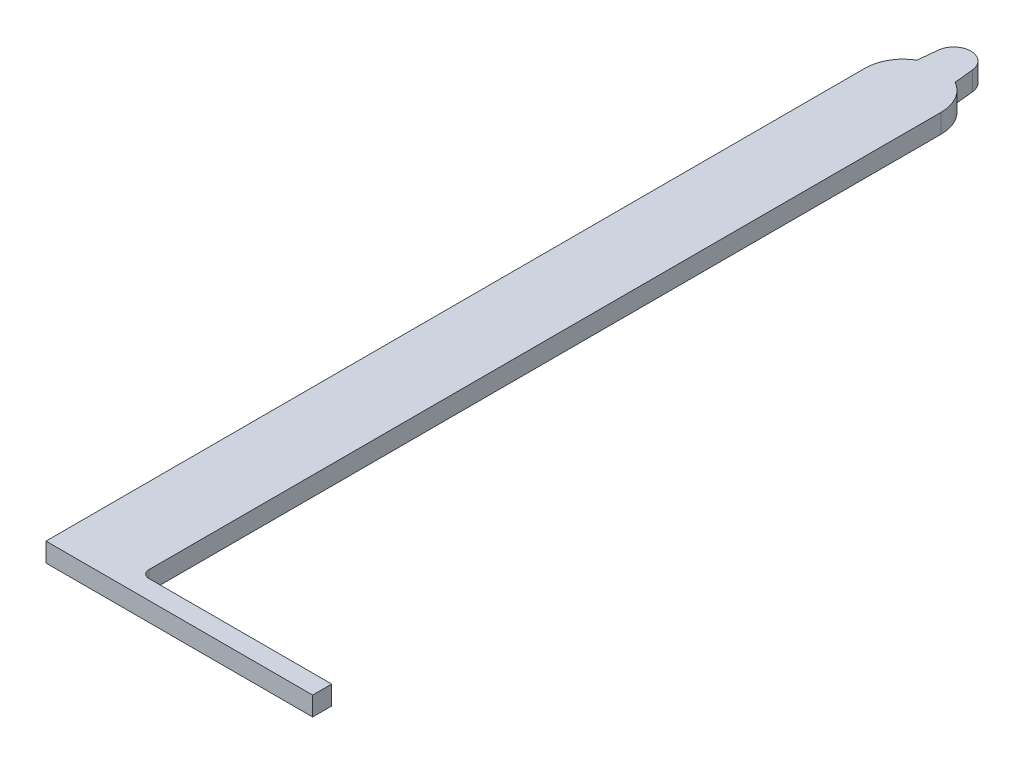
SolidWorks part; units mm, degrees
ref_plane "Front Plane" through (0, 0, 0) normal (0, 0, 1) x (1, 0, 0)
ref_plane "Top Plane" through (0, 0, 0) normal (0, 1, 0) x (1, 0, 0)
ref_plane "Right Plane" through (0, 0, 0) normal (1, 0, 0) x (0, 0, -1)
sketch "Sketch1" plane through (0, 0, 0) normal (0, 1, 0) x (1, 0, 0)
  line L1 (-12.7, 0) -> (12.7, 0)
  line L2 (-12.7, 0) -> (-12.7, -266.7)
  line L3 (-12.7, -266.7) -> (12.7, -266.7)
  line L4 (12.7, 0) -> (12.7, -266.7)
  circle A0 centre (0, 0) radius 12.7
  dimension "D1" = 25.4
  dimension "D2" = 266.7
extrude "Boss-Extrude1" add sketch "Sketch1" along normal blind 6.35 contours A0 L2 L3 L4 | L1 A0 | L1 A0 region at (0, 0, -5.39) region at (0, 0, 138.3216) region at (0, 0, 5.39)
sketch "Sketch2" plane through (0, 6.35, 0) normal (0, 1, 0) x (1, 0, 0)
  line L1 (-12.7, -266.7) -> (76.2, -266.7)
  line L2 (-12.7, -266.7) -> (-12.7, -273.05)
  line L3 (-12.7, -273.05) -> (76.2, -273.05)
  line L4 (76.2, -266.7) -> (76.2, -273.05)
  dimension "D1" = 88.9
  dimension "D2" = 6.35
extrude "Boss-Extrude2" add sketch "Sketch2" against normal up to surface (6.35 mm away) up to face at (0, 0, 130.175)
fillet "Fillet1" radius 2.54 1 edges
sketch "Sketch3" plane through (0, 0, 0) normal (0, -1, 0) x (-1, 0, 0)
  line L4 (-7.3841, 1.2138) -> (7.3841, 1.2138)
  line L6 (-7.3841, 1.2138) -> (-5.6981, 17.4684)
  line L7 (5.6981, 17.4684) -> (7.3841, 1.2138)
  line L8 (-7.3841, 1.2138) -> (-5.6981, 17.4684)
  line L9 (5.6981, 17.4684) -> (7.3841, 1.2138)
  arc A3 (5.6981, 17.4684) -> (-5.6981, 17.4684) centre (0, 16.8774) ccw
  arc A4 (5.6981, 17.4684) -> (-5.6981, 17.4684) centre (0, 16.8774) ccw
  dimension "D1" = 3.175
extrude "Boss-Extrude3" add sketch "Sketch3" against normal up to surface (6.35 mm away) up to face at (28.2277, 6.35, 171.3437)
